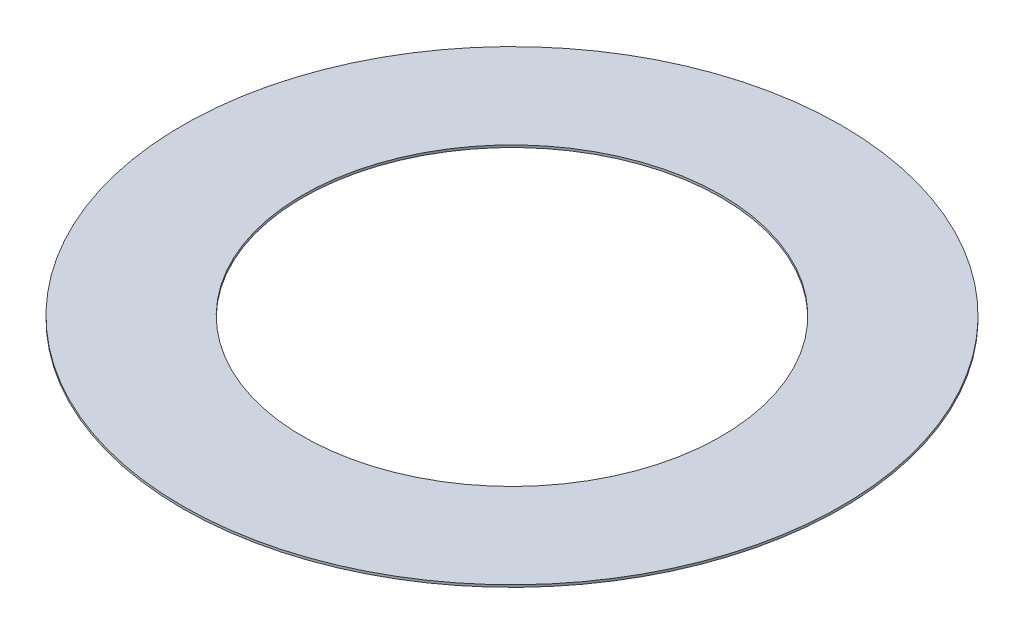
SolidWorks part; units mm, degrees
material "Plain Carbon Steel"
ref_plane "Front Plane" through (0, 0, 0) normal (0, 0, 1) x (1, 0, 0)
ref_plane "Top Plane" through (0, 0, 0) normal (0, 1, 0) x (1, 0, 0)
ref_plane "Right Plane" through (0, 0, 0) normal (1, 0, 0) x (0, 0, -1)
sketch "Sketch1" plane through (0, 0, 0) normal (0, 0, 1) x (1, 0, 0)
  line L0 (-109.5, 13.67) -> (-109.5, 12.91) construction
  line L1 (-69.5, 12.91) -> (-109.5, 12.91) construction
  line L2 (-69.5, 13.67) -> (-69.5, 12.91) construction
  line L3 (-69.5, 13.67) -> (-109.5, 13.67) construction
  line L4 (-109.5, 13.67) -> (-109.5, 12.91)
  line L5 (-69.5, 12.91) -> (-109.5, 12.91)
  line L6 (-69.5, 13.67) -> (-69.5, 12.91)
  line L7 (-69.5, 13.67) -> (-109.5, 13.67)
  line L8 (0, -200069.0475) -> (0, 200086.9028) construction
  line L9 (0, -200069.0475) -> (0, 200086.9028) construction
revolve "Revolve1" add sketch "Sketch1" angle 360 about L9
